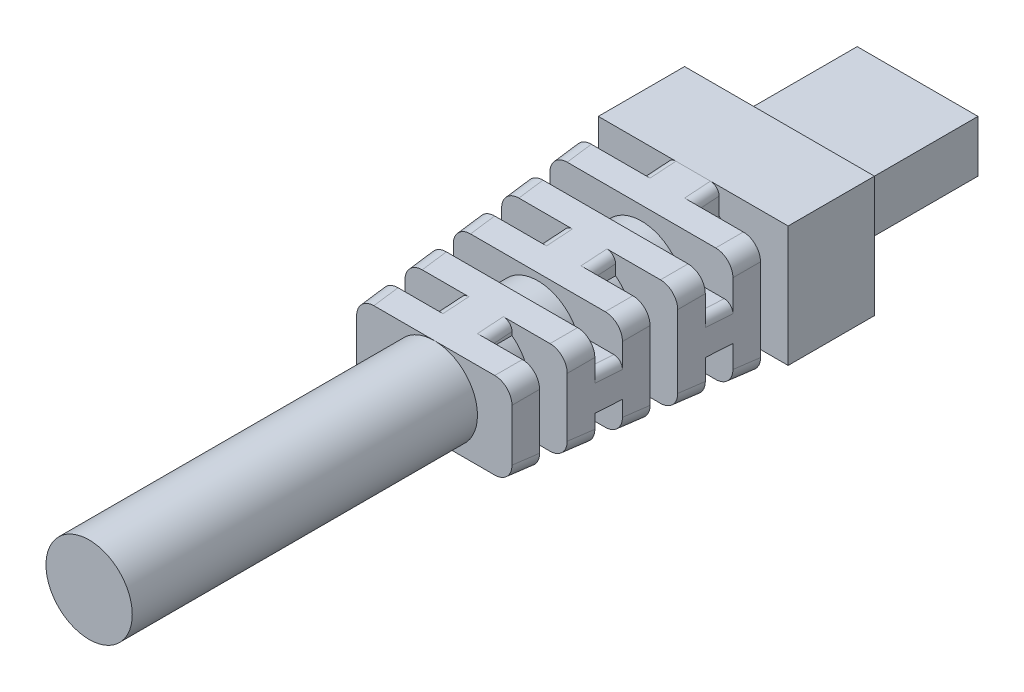
SolidWorks part; units mm, degrees
ref_plane "Ön Düzlem" through (0, 0, 0) normal (0, 0, 1) x (1, 0, 0)
ref_plane "Üst Düzlem" through (0, 0, 0) normal (0, 1, 0) x (1, 0, 0)
ref_plane "Sağ Düzlem" through (0, 0, 0) normal (1, 0, 0) x (0, 0, -1)
sketch "Sketch1" plane through (0, 0, 0) normal (0, 0, 1) x (1, 0, 0)
  line L1 (-61.3467, -20.0724) -> (-54.3467, -20.0724)
  line L2 (-61.3467, -20.0724) -> (-61.3467, -23.0724)
  line L3 (-61.3467, -23.0724) -> (-54.3467, -23.0724)
  line L4 (-54.3467, -20.0724) -> (-54.3467, -23.0724)
  dimension "D1" = 7
  dimension "D2" = 3
extrude "Boss-Extrude1" add sketch "Sketch1" along normal blind 8
sketch "Sketch2" plane through (0, 0, 8) normal (0, 0, 1) x (1, 0, 0)
  line L0 (-54.3467, -20.0724) -> (-61.3467, -20.0724) construction
  line L1 (-63.3467, -18.0724) -> (-52.3467, -18.0724)
  line L2 (-63.3467, -18.0724) -> (-63.3467, -25.0724)
  line L3 (-63.3467, -25.0724) -> (-52.3467, -25.0724)
  line L4 (-52.3467, -18.0724) -> (-52.3467, -25.0724)
  line L5 (-54.3467, -23.0724) -> (-54.3467, -20.0724) construction
  line L6 (-61.3467, -23.0724) -> (-54.3467, -23.0724) construction
  line L7 (-61.3467, -20.0724) -> (-61.3467, -23.0724) construction
  dimension "D1" = 2
  dimension "D2" = 2
  dimension "D3" = 2
  dimension "D4" = 2
extrude "Boss-Extrude2" add sketch "Sketch2" along normal blind 20
chamfer "Chamfer2" distance 15 distance2 1 4 edges at (-57.8467, -25.0724, 28) (-52.3467, -21.5724, 28) (-57.8467, -18.0724, 28) (-63.3467, -21.5724, 28) first distance on face at (-57.8467, -25.0724, 18) first distance on face at (-52.3467, -21.5724, 18) first distance on face at (-57.8467, -18.0724, 18) first distance on face at (-63.3467, -21.5724, 18)
ref_plane "Plane1" through (-57.8467, 0, 0) normal (-1, 0, 0) x (0, 0, 1)
sketch "Sketch5" plane through (-52.3467, 0, 0) normal (1, 0, 0) x (0, 0, -1)
  line L0 (-13, -18.0724) -> (-8, -18.0724) construction
  line L1 (-26.5, -18.0724) -> (-25, -18.0724)
  line L2 (-26.5, -18.0724) -> (-26.5, -20.5724)
  line L3 (-26.5, -20.5724) -> (-25, -20.5724)
  line L4 (-25, -18.0724) -> (-25, -20.5724)
  line L5 (-28, -18.0724) -> (-28, -25.0724) construction
  line L6 (-23.5, -18.0724) -> (-22, -18.0724)
  line L7 (-23.5, -18.0724) -> (-23.5, -20.5724)
  line L8 (-23.5, -20.5724) -> (-22, -20.5724)
  line L9 (-22, -18.0724) -> (-22, -20.5724)
  line L10 (-20.5, -18.0724) -> (-19, -18.0724)
  line L11 (-20.5, -18.0724) -> (-20.5, -20.5724)
  line L12 (-20.5, -20.5724) -> (-19, -20.5724)
  line L13 (-19, -18.0724) -> (-19, -20.5724)
  line L14 (-17.5, -18.0724) -> (-16, -18.0724)
  line L15 (-17.5, -18.0724) -> (-17.5, -20.5724)
  line L16 (-17.5, -20.5724) -> (-16, -20.5724)
  line L17 (-16, -18.0724) -> (-16, -20.5724)
  line L18 (-14.5, -18.0724) -> (-13, -18.0724)
  line L19 (-14.5, -18.0724) -> (-14.5, -20.5724)
  line L20 (-14.5, -20.5724) -> (-13, -20.5724)
  line L21 (-13, -18.0724) -> (-13, -20.5724)
  line L22 (-23.5, -22.5724) -> (-22, -22.5724)
  line L23 (-23.5, -22.5724) -> (-23.5, -25.0724)
  line L24 (-23.5, -25.0724) -> (-22, -25.0724)
  line L25 (-22, -22.5724) -> (-22, -25.0724)
  line L26 (-20.5, -22.5724) -> (-19, -22.5724)
  line L27 (-20.5, -22.5724) -> (-20.5, -25.0724)
  line L28 (-20.5, -25.0724) -> (-19, -25.0724)
  line L29 (-19, -22.5724) -> (-19, -25.0724)
  line L30 (-17.5, -22.5724) -> (-16, -22.5724)
  line L31 (-17.5, -22.5724) -> (-17.5, -25.0724)
  line L32 (-17.5, -25.0724) -> (-16, -25.0724)
  line L33 (-16, -22.5724) -> (-16, -25.0724)
  line L34 (-14.5, -22.5724) -> (-13, -22.5724)
  line L35 (-14.5, -22.5724) -> (-14.5, -25.0724)
  line L36 (-14.5, -25.0724) -> (-13, -25.0724)
  line L37 (-13, -22.5724) -> (-13, -25.0724)
  line L38 (-26.5, -22.5724) -> (-25, -22.5724)
  line L39 (-26.5, -22.5724) -> (-26.5, -25.0724)
  line L40 (-26.5, -25.0724) -> (-25, -25.0724)
  line L41 (-25, -22.5724) -> (-25, -25.0724)
  dimension "D1" = 1.5
  dimension "D2" = 1.5
  dimension "D3" = 2.5
  dimension "D4" = 5
  dimension "D5" = 2
extrude "Cut-Extrude2" cut sketch "Sketch5" against normal blind 4
ref_plane "Plane8" through (-57.8467, 0, 0) normal (1, 0, 0) x (0, 0, -1)
mirror "Mirror2" about plane through (-57.8467, 0, 0) normal (1, 0, 0) of "Cut-Extrude2"
fillet "Fillet2" radius 1 20 edges at (-62.5967, -18.8224, 24.25) (-62.7967, -18.6224, 21.25) (-62.9967, -18.4224, 18.25) (-63.1967, -18.2224, 15.25) (-62.5967, -24.3224, 24.25) (-62.7967, -24.5224, 21.25) (-62.9967, -24.7224, 18.25) (-63.1967, -24.9224, 15.25) (-52.4967, -24.9224, 15.25) (-52.6967, -24.7224, 18.25) (-52.8967, -24.5224, 21.25) (-53.0967, -24.3224, 24.25) (-53.0967, -18.8224, 24.25) (-52.8967, -18.6224, 21.25) (-52.6967, -18.4224, 18.25) (-52.4967, -18.2224, 15.25) (-53.2967, -24.1224, 27.25) (-53.2967, -19.0224, 27.25) (-62.3967, -24.1224, 27.25) (-62.3967, -19.0224, 27.25)
sketch "Sketch6" plane through (-63.3467, 0, 0) normal (-1, 0, 0) x (0, 0, 1)
  line L1 (13, -20.5724) -> (14.5, -20.5724)
  line L2 (13, -20.5724) -> (13, -22.5724)
  line L3 (13, -22.5724) -> (14.5, -22.5724)
  line L4 (14.5, -20.5724) -> (14.5, -22.5724)
  line L5 (19, -20.5724) -> (20.5, -20.5724)
  line L6 (19, -20.5724) -> (19, -22.5724)
  line L7 (19, -22.5724) -> (20.5, -22.5724)
  line L8 (20.5, -20.5724) -> (20.5, -22.5724)
  line L9 (25, -20.5724) -> (26.5, -20.5724)
  line L10 (25, -20.5724) -> (25, -22.5724)
  line L11 (25, -22.5724) -> (26.5, -22.5724)
  line L12 (26.5, -20.5724) -> (26.5, -22.5724)
extrude "Cut-Extrude3" cut sketch "Sketch6" against normal blind 4
mirror "Mirror3" about plane through (-57.8467, 0, 0) normal (1, 0, 0) of "Cut-Extrude3"
ref_plane "Plane9" through (0, -21.5724, 0) normal (0, 1, 0) x (1, 0, 0)
sketch "Sketch7" plane through (0, -18.0724, 0) normal (0, 1, 0) x (1, 0, 0)
  line L1 (-59.3467, -16) -> (-56.3467, -16)
  line L2 (-59.3467, -16) -> (-59.3467, -17.5)
  line L3 (-59.3467, -17.5) -> (-56.3467, -17.5)
  line L4 (-56.3467, -16) -> (-56.3467, -17.5)
  line L5 (-59.3467, -22) -> (-56.3467, -22)
  line L6 (-59.3467, -22) -> (-59.3467, -23.5)
  line L7 (-59.3467, -23.5) -> (-56.3467, -23.5)
  line L8 (-56.3467, -22) -> (-56.3467, -23.5)
extrude "Cut-Extrude4" cut sketch "Sketch7" against normal blind 2.5
mirror "Mirror4" about plane through (0, -21.5724, 0) normal (0, 1, 0) of "Cut-Extrude4"
sketch "Sketch8" plane through (0, 0, 28) normal (0, 0, 1) x (1, 0, 0)
  circle A0 centre (-57.8467, -21.5724) radius 2.5
  dimension "D1" = 5
extrude "Boss-Extrude4" add sketch "Sketch8" against normal blind 20 and the other way blind 20
fillet "Fillet3" radius 0.5 22 edges at (-59.3467, -25.0224, 13.75) (-59.3467, -24.6224, 19.75) (-56.3467, -25.0224, 13.75) (-56.3467, -24.6224, 19.75) (-56.3467, -24.2224, 25.75) (-59.3467, -24.2224, 25.75) (-59.3467, -18.9224, 25.75) (-52.9967, -20.5724, 22.75) (-56.3467, -18.9224, 25.75) (-52.5967, -20.5724, 16.75) (-56.3467, -18.5224, 19.75) (-59.3467, -18.5224, 19.75) (-62.6967, -22.5724, 22.75) (-63.0967, -22.5724, 16.75) (-62.6967, -20.5724, 22.75) (-56.3467, -18.1224, 13.75) (-59.3467, -18.1224, 13.75) (-59.3467, -23.5724, 13.75) (-59.3467, -19.5724, 13.75) (-63.0967, -20.5724, 16.75) (-59.3467, -19.5724, 19.75) (-60.138, -20.5724, 22.75)
